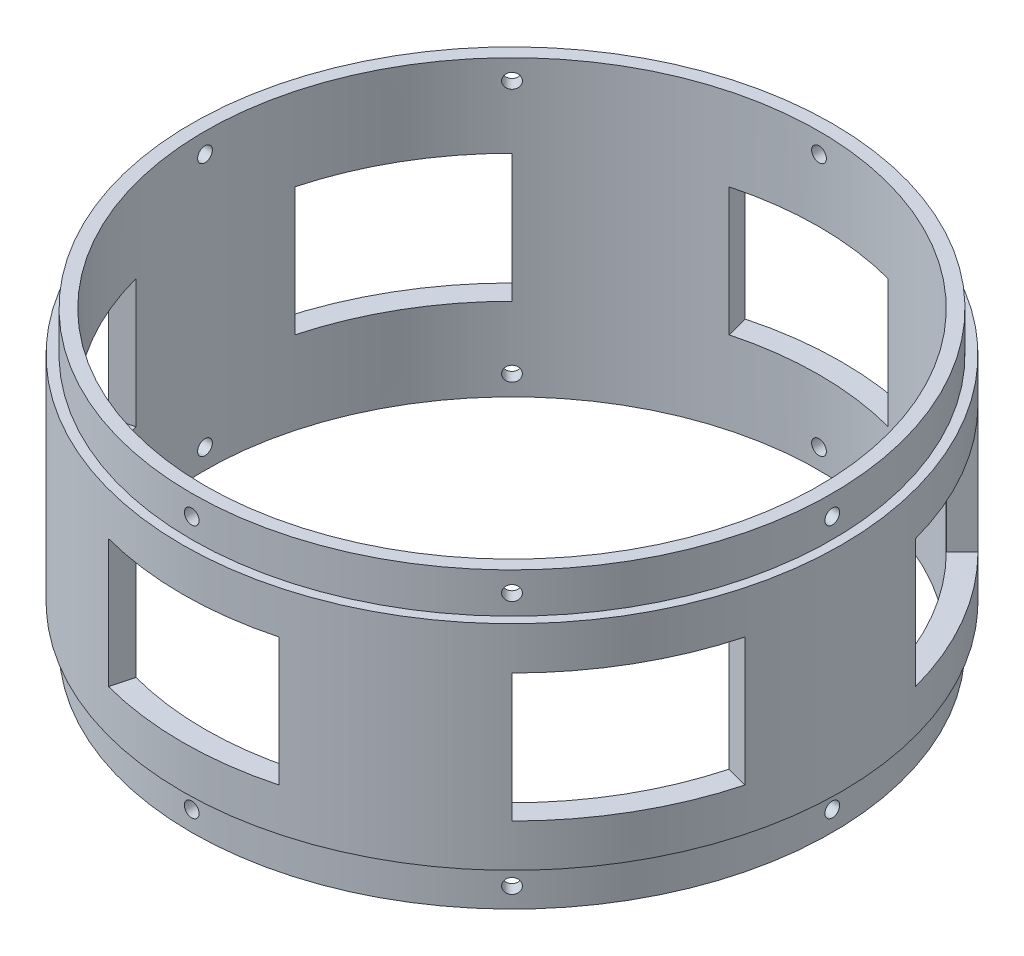
SolidWorks part; units mm, degrees
ref_plane "Front Plane" through (0, 0, 0) normal (0, 0, 1) x (1, 0, 0)
ref_plane "Top Plane" through (0, 0, 0) normal (0, 1, 0) x (1, 0, 0)
ref_plane "Right Plane" through (0, 0, 0) normal (1, 0, 0) x (0, 0, -1)
sketch "Sketch1" plane through (0, 0, 0) normal (0, 1, 0) x (1, 0, 0)
  line L0 (0, 0) -> (-20.2808, 75.689)
  line L1 (0, 0) -> (20.2808, 75.689)
  line L2 (0, 0) -> (0, 72.1431) construction
  circle A0 centre (0, 0) radius 78.359
  circle A1 centre (0, 0) radius 73.025
  circle A2 centre (0, 0) radius 76.1746
  dimension "D1" = 156.718
  dimension "D2" = 146.05
  dimension "D3" = 152.3492
  dimension "D4" = 30
extrude "Boss-Extrude1" add sketch "Sketch1" along normal blind 50.8 contours L2 A2 L1 A0 | L2 A1 L1 A2 | L2 A2 L1 A1 | L2 A0 L1 A2 | A2 L2 A1 L0 | A0 L2 A2 L0 | A2 L2 A0 L0 | A1 L2 A2 L0 region at (-45.7553, 0, 59.6294) region at (0, 0, -73.7615) region at (-46.5059, 0, 60.6077) region at (0, 0, -76.3923)
ref_plane "Plane1" through (0, 25.4, 0) normal (0, 1, 0) x (1, 0, 0)
extrude "Boss-Extrude2" add sketch "Sketch1<3>" along normal blind 9.525 from surface contours A2 L2 A1 L0 | L2 A2 L1 A1 | L2 A1 L1 A2 | A1 L2 A2 L0 region at (-45.7553, 0, 59.6294) region at (0, 0, -73.7615) starting at face at (0, 50.8, 73.025)
sketch "Sketch1<3>" plane through (0, 0, 0) normal (0, 1, 0) x (1, 0, 0) same geometry as "Sketch1"
extrude "Boss-Extrude3" add sketch "Sketch1<4>" against normal blind 9.525 contours A2 L2 A1 L0 | A1 L2 A2 L0 | L2 A1 L1 A2 | L2 A2 L1 A1 region at (-45.7553, 0, 59.6294) region at (0, 0, -73.7615)
sketch "Sketch1<4>" plane through (0, 0, 0) normal (0, 1, 0) x (1, 0, 0) same geometry as "Sketch1"
ref_plane "Plane2" through (0, 0, -76.1746) normal (0, 0, -1) x (-1, 0, 0)
ref_axis "Axis1" through (0, 0, 0) along (0, 1, 0)
sketch "Sketch3" plane through (0, 0, -76.1746) normal (0, 0, -1) x (-1, 0, 0)
  line L0 (76.1746, 0) -> (-76.1746, 0) construction
  line L1 (-76.1746, -9.525) -> (76.1746, -9.525) construction
  line L2 (76.1746, 50.8) -> (-76.1746, 50.8) construction
  line L3 (76.1746, 60.325) -> (-76.1746, 60.325) construction
  line L4 (76.1746, 0) -> (-76.1746, 0)
  line L5 (-76.1746, -9.525) -> (76.1746, -9.525)
  line L6 (76.1746, 50.8) -> (-76.1746, 50.8)
  line L7 (76.1746, 60.325) -> (-76.1746, 60.325)
  line L8 (0, 60.325) -> (0, 50.8)
  line L9 (0, 0) -> (0, -9.525)
  circle A0 centre (0, 55.5625) radius 1.75
  circle A1 centre (0, -4.7625) radius 1.75
  point P12 (0, 55.5625)
  point P13 (0, -4.7625)
  point P14 (-77.5445, 179.1871)
  dimension "D1" = 3.5
extrude "Cut-Extrude2" cut sketch "Sketch3" against normal up to next contours L8 A0 | L8 A0 | L9 A1 | L9 A1 region at (-0.7427, 55.5625, -76.1746) region at (0.7427, 55.5625, -76.1746) region at (-0.7427, -4.7625, -76.1746) region at (0.7427, -4.7625, -76.1746)
extrude "Cut-Extrude3" cut sketch "Sketch1<7>" against normal blind 15.24 and the other way blind 15.24 from surface contours L2 A1 L1 A2 | A1 L2 A2 L0 | A2 L2 A0 L0 | L2 A2 L1 A0 region at (0, 0, -73.7615) region at (0, 0, -76.3923) starting at plane "Plane1"
sketch "Sketch1<7>" plane through (0, 0, 0) normal (0, 1, 0) x (1, 0, 0) same geometry as "Sketch1"
pattern_circular "CirPattern2" count 6 over 360 about axis through (0, 0, 0) along (0, 1, 0) of "Cut-Extrude3"
pattern_circular "CirPattern3" count 8 over 360 about axis through (0, 0, 0) along (0, 1, 0) of "Cut-Extrude2"
equation "\"AB_Coupler_OD_Length\"= 2in"
equation "\"AB_Coupling_Section_Length\"= 0.375in"
equation "\"AB_Coupler_Length\"= \"AB_Coupler_OD_Length\" + \"AB_Coupling_Section_Length\" * 2"
equation "\"D1@Boss-Extrude2\"=\"AB_Coupling_Section_Length\""
equation "\"D1@Boss-Extrude3\"=\"AB_Coupling_Section_Length\""
equation "\"D1@Boss-Extrude1\" = \"AB_Coupler_OD_Length\""
equation "\"Cutout_Angle\"= 30"
equation "\"AB_Coupler_Num_Screws\"= 8"
equation "\"Num_Cutouts\"= 6"
equation "\"D4@Sketch1\"=\"Cutout_Angle\""
equation "\"D1@CirPattern2\"=\"Num_Cutouts\""
equation "\"D1@CirPattern3\"=\"AB_Coupler_Num_Screws\""
equation "\"AB_Coupler_OD\"= 6.17in"
equation "\"AB_Coupler_ID\"= 5.75in"
equation "\"AB_Coupler_Surface_Diameter\"= 5.998in"
equation "\"D3@Sketch1\"=\"AB_Coupler_Surface_Diameter\""
equation "\"D2@Sketch1\"=\"AB_Coupler_ID\""
equation "\"D1@Sketch1\"=\"AB_Coupler_OD\""
equation "\"AB_Coupling_Screw_Diameter\"= 3.5mm"
